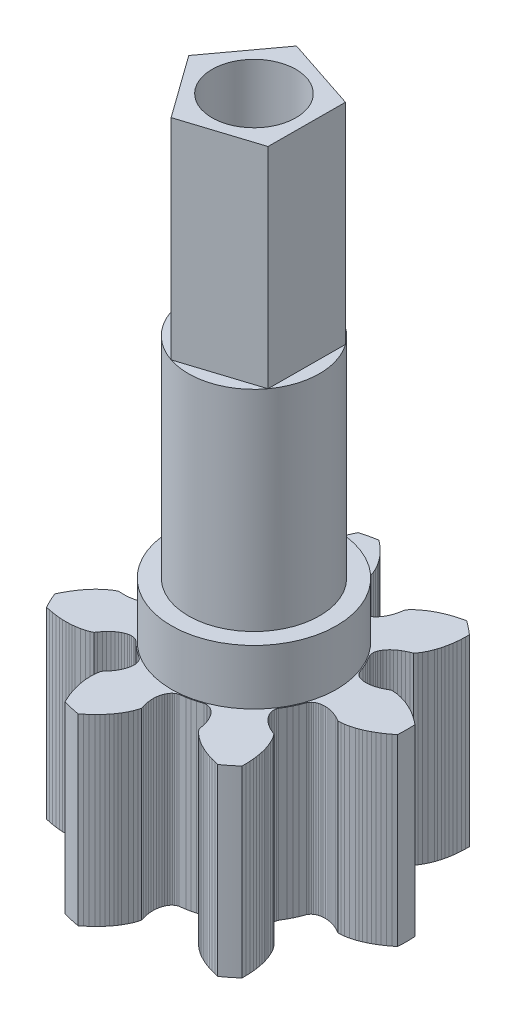
SolidWorks part; units mm, degrees
ref_plane "Front Plane" through (0, 0, 0) normal (0, 0, 1) x (1, 0, 0)
ref_plane "Top Plane" through (0, 0, 0) normal (0, 1, 0) x (1, 0, 0)
ref_plane "Right Plane" through (0, 0, 0) normal (1, 0, 0) x (0, 0, -1)
sketch "Sketch1" plane through (0, 0, 0) normal (0, 1, 0) x (1, 0, 0)
  circle A0 centre (0, 0) radius 3.15
  dimension "D1" = 6.3
extrude "Boss-Extrude1" add sketch "Sketch1" along normal blind 2.1
sketch "Sketch2" plane through (0, 2.1, 0) normal (0, 1, 0) x (1, 0, 0)
  circle A0 centre (0, 0) radius 2.5
  dimension "D1" = 5
extrude "Boss-Extrude3" add sketch "Sketch2" along normal blind 16
sketch "Sketch4" plane through (0, 0, 0) normal (0, -1, 0) x (1, 0, 0)
  line L420 (-1.6777, -5.4575) -> (-1.7402, -5.3144)
  line L421 (-1.7402, -5.3144) -> (-1.7939, -5.1757)
  line L422 (-1.7939, -5.1757) -> (-1.8392, -5.0423)
  line L423 (-1.8392, -5.0423) -> (-1.8764, -4.916)
  line L424 (-1.8764, -4.916) -> (-1.9071, -4.7932)
  line L425 (-1.9071, -4.7932) -> (-1.9311, -4.676)
  line L426 (-1.9311, -4.676) -> (-1.9488, -4.5668)
  line L427 (-1.9488, -4.5668) -> (-1.961, -4.464)
  line L428 (-1.961, -4.464) -> (-1.9715, -4.2798)
  line L429 (-1.9715, -4.2798) -> (-1.9674, -4.1246)
  line L430 (-1.9674, -4.1246) -> (-1.9537, -4.0009)
  line L431 (-1.9537, -4.0009) -> (-1.9303, -3.8867)
  line L432 (-1.9303, -3.8867) -> (-1.8594, -3.8097)
  line L433 (-1.8594, -3.8097) -> (-1.7784, -3.7125)
  line L434 (-1.7784, -3.7125) -> (-1.7087, -3.6155)
  line L435 (-1.7087, -3.6155) -> (-1.6501, -3.5195)
  line L436 (-1.6501, -3.5195) -> (-1.6023, -3.4251)
  line L437 (-1.6023, -3.4251) -> (-1.5652, -3.3333)
  line L438 (-1.5652, -3.3333) -> (-1.5384, -3.2446)
  line L439 (-1.5384, -3.2446) -> (-1.5215, -3.1597)
  line L440 (-1.5215, -3.1597) -> (-1.5143, -3.0795)
  line L441 (-1.5143, -3.0795) -> (-1.5162, -3.0043)
  line L442 (-1.5162, -3.0043) -> (-1.5269, -2.935)
  line L443 (-1.5269, -2.935) -> (-1.5457, -2.8721)
  line L444 (-1.5457, -2.8721) -> (-1.5723, -2.8162)
  line L445 (-1.5723, -2.8162) -> (-1.606, -2.7677)
  line L446 (-1.606, -2.7677) -> (-1.6572, -2.7183)
  line L447 (-1.6572, -2.7183) -> (-1.8447, -2.5928)
  line L448 (-1.8447, -2.5928) -> (-1.984, -2.4878)
  line L449 (-1.984, -2.4878) -> (-2.1173, -2.3754)
  line L450 (-2.1173, -2.3754) -> (-2.2814, -2.2205)
  line L451 (-2.2814, -2.2205) -> (-2.341, -2.1815)
  line L452 (-2.341, -2.1815) -> (-2.3957, -2.1595)
  line L453 (-2.3957, -2.1595) -> (-2.4562, -2.146)
  line L454 (-2.4562, -2.146) -> (-2.5217, -2.1417)
  line L455 (-2.5217, -2.1417) -> (-2.5917, -2.1467)
  line L456 (-2.5917, -2.1467) -> (-2.6653, -2.1615)
  line L457 (-2.6653, -2.1615) -> (-2.742, -2.1865)
  line L458 (-2.742, -2.1865) -> (-2.8209, -2.2218)
  line L459 (-2.8209, -2.2218) -> (-2.9014, -2.2676)
  line L460 (-2.9014, -2.2676) -> (-2.9827, -2.3243)
  line L461 (-2.9827, -2.3243) -> (-3.0641, -2.3918)
  line L462 (-3.0641, -2.3918) -> (-3.1447, -2.4703)
  line L463 (-3.1447, -2.4703) -> (-3.2237, -2.5599)
  line L464 (-3.2237, -2.5599) -> (-3.3005, -2.6605)
  line L465 (-3.3005, -2.6605) -> (-3.3598, -2.7467)
  line L466 (-3.3598, -2.7467) -> (-3.4659, -2.795)
  line L467 (-3.4659, -2.795) -> (-3.5835, -2.8358)
  line L468 (-3.5835, -2.8358) -> (-3.7338, -2.8744)
  line L469 (-3.7338, -2.8744) -> (-3.9158, -2.9052)
  line L470 (-3.9158, -2.9052) -> (-4.0187, -2.9161)
  line L471 (-4.0187, -2.9161) -> (-4.1291, -2.9232)
  line L472 (-4.1291, -2.9232) -> (-4.2487, -2.9258)
  line L473 (-4.2487, -2.9258) -> (-4.3752, -2.9233)
  line L474 (-4.3752, -2.9233) -> (-4.5067, -2.9151)
  line L475 (-4.5067, -2.9151) -> (-4.6468, -2.9006)
  line L476 (-4.6468, -2.9006) -> (-4.794, -2.8791)
  line L477 (-4.794, -2.8791) -> (-4.9474, -2.85)
  line L478 (-4.9474, -2.85) -> (-5.0902, -2.8167)
  line L479 (-5.3759, -2.2235) -> (-5.3129, -2.0911)
  line L480 (-5.3129, -2.0911) -> (-5.2399, -1.953)
  line L481 (-5.2399, -1.953) -> (-5.165, -1.8245)
  line L482 (-5.165, -1.8245) -> (-5.089, -1.7059)
  line L483 (-5.089, -1.7059) -> (-5.0134, -1.5981)
  line L484 (-5.0134, -1.5981) -> (-4.9365, -1.4976)
  line L485 (-4.9365, -1.4976) -> (-4.8599, -1.4057)
  line L486 (-4.8599, -1.4057) -> (-4.7855, -1.3238)
  line L487 (-4.7855, -1.3238) -> (-4.7128, -1.2502)
  line L488 (-4.7128, -1.2502) -> (-4.5753, -1.1271)
  line L489 (-4.5753, -1.1271) -> (-4.4514, -1.0336)
  line L490 (-4.4514, -1.0336) -> (-4.3462, -0.9671)
  line L491 (-4.3462, -0.9671) -> (-4.2422, -0.9142)
  line L492 (-4.2422, -0.9142) -> (-4.1379, -0.9217)
  line L493 (-4.1379, -0.9217) -> (-4.0114, -0.9244)
  line L494 (-4.0114, -0.9244) -> (-3.8921, -0.9184)
  line L495 (-3.8921, -0.9184) -> (-3.7804, -0.9043)
  line L496 (-3.7804, -0.9043) -> (-3.6769, -0.8828)
  line L497 (-3.6769, -0.8828) -> (-3.5819, -0.8546)
  line L498 (-3.5819, -0.8546) -> (-3.4959, -0.8203)
  line L499 (-3.4959, -0.8203) -> (-3.4191, -0.7805)
  line L500 (-3.4191, -0.7805) -> (-3.3518, -0.7361)
  line L501 (-3.3518, -0.7361) -> (-3.2942, -0.6878)
  line L502 (-3.2942, -0.6878) -> (-3.2467, -0.6363)
  line L503 (-3.2467, -0.6363) -> (-3.2093, -0.5823)
  line L504 (-3.2093, -0.5823) -> (-3.1821, -0.5267)
  line L505 (-3.1821, -0.5267) -> (-3.1652, -0.4701)
  line L506 (-3.1652, -0.4701) -> (-3.1585, -0.3992)
  line L507 (-3.1585, -0.3992) -> (-3.1773, -0.1744)
  line L508 (-3.1773, -0.1744) -> (-3.1821, 0)
  line L509 (-3.1821, 0) -> (-3.1773, 0.1743)
  line L510 (-3.1773, 0.1743) -> (-3.1585, 0.3991)
  line L511 (-3.1585, 0.3991) -> (-3.1652, 0.47)
  line L512 (-3.1652, 0.47) -> (-3.1821, 0.5266)
  line L513 (-3.1821, 0.5266) -> (-3.2093, 0.5822)
  line L514 (-3.2093, 0.5822) -> (-3.2467, 0.6362)
  line L515 (-3.2467, 0.6362) -> (-3.2942, 0.6877)
  line L516 (-3.2942, 0.6877) -> (-3.3518, 0.7361)
  line L517 (-3.3518, 0.7361) -> (-3.4191, 0.7805)
  line L518 (-3.4191, 0.7805) -> (-3.4959, 0.8202)
  line L519 (-3.4959, 0.8202) -> (-3.5819, 0.8545)
  line L520 (-3.5819, 0.8545) -> (-3.6769, 0.8828)
  line L521 (-3.6769, 0.8828) -> (-3.7804, 0.9043)
  line L522 (-3.7804, 0.9043) -> (-3.8921, 0.9183)
  line L523 (-3.8921, 0.9183) -> (-4.0114, 0.9243)
  line L524 (-4.0114, 0.9243) -> (-4.1379, 0.9216)
  line L525 (-4.1379, 0.9216) -> (-4.2422, 0.9142)
  line L526 (-4.2422, 0.9142) -> (-4.3462, 0.967)
  line L527 (-4.3462, 0.967) -> (-4.4514, 1.0335)
  line L528 (-4.4514, 1.0335) -> (-4.5753, 1.127)
  line L529 (-4.5753, 1.127) -> (-4.7128, 1.2501)
  line L530 (-4.7128, 1.2501) -> (-4.7855, 1.3238)
  line L531 (-4.7855, 1.3238) -> (-4.8599, 1.4056)
  line L532 (-4.8599, 1.4056) -> (-4.9365, 1.4975)
  line L533 (-4.9365, 1.4975) -> (-5.0134, 1.598)
  line L534 (-5.0134, 1.598) -> (-5.089, 1.7059)
  line L535 (-5.089, 1.7059) -> (-5.165, 1.8244)
  line L536 (-5.165, 1.8244) -> (-5.2399, 1.9529)
  line L537 (-5.2399, 1.9529) -> (-5.3129, 2.0911)
  line L538 (-5.3129, 2.0911) -> (-5.3759, 2.2234)
  line L539 (-5.0902, 2.8167) -> (-4.9474, 2.8499)
  line L540 (-4.9474, 2.8499) -> (-4.794, 2.879)
  line L541 (-4.794, 2.879) -> (-4.6468, 2.9005)
  line L542 (-4.6468, 2.9005) -> (-4.5067, 2.9151)
  line L543 (-4.5067, 2.9151) -> (-4.3752, 2.9232)
  line L544 (-4.3752, 2.9232) -> (-4.2487, 2.9257)
  line L545 (-4.2487, 2.9257) -> (-4.1291, 2.9231)
  line L546 (-4.1291, 2.9231) -> (-4.0187, 2.916)
  line L547 (-4.0187, 2.916) -> (-3.9158, 2.9051)
  line L548 (-3.9158, 2.9051) -> (-3.7338, 2.8743)
  line L549 (-3.7338, 2.8743) -> (-3.5835, 2.8358)
  line L550 (-3.5835, 2.8358) -> (-3.4659, 2.7949)
  line L551 (-3.4659, 2.7949) -> (-3.3598, 2.7466)
  line L552 (-3.3598, 2.7466) -> (-3.3005, 2.6604)
  line L553 (-3.3005, 2.6604) -> (-3.2237, 2.5598)
  line L554 (-3.2237, 2.5598) -> (-3.1447, 2.4703)
  line L555 (-3.1447, 2.4703) -> (-3.0641, 2.3918)
  line L556 (-3.0641, 2.3918) -> (-2.9827, 2.3242)
  line L557 (-2.9827, 2.3242) -> (-2.9014, 2.2676)
  line L558 (-2.9014, 2.2676) -> (-2.8209, 2.2217)
  line L559 (-2.8209, 2.2217) -> (-2.742, 2.1864)
  line L560 (-2.742, 2.1864) -> (-2.6653, 2.1615)
  line L561 (-2.6653, 2.1615) -> (-2.5917, 2.1466)
  line L562 (-2.5917, 2.1466) -> (-2.5217, 2.1416)
  line L563 (-2.5217, 2.1416) -> (-2.4562, 2.146)
  line L564 (-2.4562, 2.146) -> (-2.3957, 2.1594)
  line L565 (-2.3957, 2.1594) -> (-2.341, 2.1815)
  line L566 (-2.341, 2.1815) -> (-2.2814, 2.2205)
  line L567 (-2.2814, 2.2205) -> (-2.1173, 2.3753)
  line L568 (-2.1173, 2.3753) -> (-1.984, 2.4878)
  line L569 (-1.984, 2.4878) -> (-1.8447, 2.5927)
  line L570 (-1.8447, 2.5927) -> (-1.6572, 2.7182)
  line L571 (-1.6572, 2.7182) -> (-1.606, 2.7676)
  line L572 (-1.606, 2.7676) -> (-1.5723, 2.8161)
  line L573 (-1.5723, 2.8161) -> (-1.5457, 2.8721)
  line L574 (-1.5457, 2.8721) -> (-1.5269, 2.935)
  line L575 (-1.5269, 2.935) -> (-1.5162, 3.0043)
  line L576 (-1.5162, 3.0043) -> (-1.5143, 3.0794)
  line L577 (-1.5143, 3.0794) -> (-1.5215, 3.1597)
  line L578 (-1.5215, 3.1597) -> (-1.5384, 3.2445)
  line L579 (-1.5384, 3.2445) -> (-1.5652, 3.3332)
  line L580 (-1.5652, 3.3332) -> (-1.6023, 3.4251)
  line L581 (-1.6023, 3.4251) -> (-1.6501, 3.5194)
  line L582 (-1.6501, 3.5194) -> (-1.7087, 3.6154)
  line L583 (-1.7087, 3.6154) -> (-1.7784, 3.7125)
  line L584 (-1.7784, 3.7125) -> (-1.8594, 3.8097)
  line L585 (-1.8594, 3.8097) -> (-1.9303, 3.8866)
  line L586 (-1.9303, 3.8866) -> (-1.9537, 4.0009)
  line L587 (-1.9537, 4.0009) -> (-1.9674, 4.1246)
  line L588 (-1.9674, 4.1246) -> (-1.9715, 4.2797)
  line L589 (-1.9715, 4.2797) -> (-1.961, 4.464)
  line L590 (-1.961, 4.464) -> (-1.9488, 4.5668)
  line L591 (-1.9488, 4.5668) -> (-1.9311, 4.6759)
  line L592 (-1.9311, 4.6759) -> (-1.9071, 4.7932)
  line L593 (-1.9071, 4.7932) -> (-1.8764, 4.9159)
  line L594 (-1.8764, 4.9159) -> (-1.8392, 5.0423)
  line L595 (-1.8392, 5.0423) -> (-1.7939, 5.1756)
  line L596 (-1.7939, 5.1756) -> (-1.7402, 5.3143)
  line L597 (-1.7402, 5.3143) -> (-1.6777, 5.4575)
  line L598 (-1.6777, 5.4575) -> (-1.6135, 5.5893)
  line L599 (-0.9715, 5.7358) -> (-0.8565, 5.6449)
  line L600 (-0.8565, 5.6449) -> (-0.7381, 5.543)
  line L601 (-0.7381, 5.543) -> (-0.6295, 5.4414)
  line L602 (-0.6295, 5.4414) -> (-0.5308, 5.3409)
  line L603 (-0.5308, 5.3409) -> (-0.4425, 5.2432)
  line L604 (-0.4425, 5.2432) -> (-0.3616, 5.1459)
  line L605 (-0.3616, 5.1459) -> (-0.2891, 5.0507)
  line L606 (-0.2891, 5.0507) -> (-0.2258, 4.96)
  line L607 (-0.2258, 4.96) -> (-0.1702, 4.8727)
  line L608 (-0.1702, 4.8727) -> (-0.0808, 4.7113)
  line L609 (-0.0808, 4.7113) -> (-0.0172, 4.5697)
  line L610 (-0.0172, 4.5697) -> (0.0242, 4.4523)
  line L611 (0.0242, 4.4523) -> (0.0526, 4.3392)
  line L612 (0.0526, 4.3392) -> (0.0222, 4.2391)
  line L613 (0.0222, 4.2391) -> (-0.0086, 4.1164)
  line L614 (-0.0086, 4.1164) -> (-0.0293, 3.9987)
  line L615 (-0.0293, 3.9987) -> (-0.0405, 3.8868)
  line L616 (-0.0405, 3.8868) -> (-0.0426, 3.7811)
  line L617 (-0.0426, 3.7811) -> (-0.0362, 3.6822)
  line L618 (-0.0362, 3.6822) -> (-0.0218, 3.5907)
  line L619 (-0.0218, 3.5907) -> (-0.0002, 3.5069)
  line L620 (-0.0002, 3.5069) -> (0.0281, 3.4314)
  line L621 (0.0281, 3.4314) -> (0.0624, 3.3646)
  line L622 (0.0624, 3.3646) -> (0.1021, 3.3068)
  line L623 (0.1021, 3.3068) -> (0.1464, 3.2583)
  line L624 (0.1464, 3.2583) -> (0.1946, 3.2194)
  line L625 (0.1946, 3.2194) -> (0.246, 3.1903)
  line L626 (0.246, 3.1903) -> (0.3136, 3.1681)
  line L627 (0.3136, 3.1681) -> (0.537, 3.1363)
  line L628 (0.537, 3.1363) -> (0.708, 3.1022)
  line L629 (0.708, 3.1022) -> (0.8769, 3.0588)
  line L630 (0.8769, 3.0588) -> (1.0919, 2.9904)
  line L631 (1.0919, 2.9904) -> (1.1625, 2.9811)
  line L632 (1.1625, 2.9811) -> (1.2214, 2.985)
  line L633 (1.2214, 2.985) -> (1.2817, 2.9991)
  line L634 (1.2817, 2.9991) -> (1.3427, 3.0236)
  line L635 (1.3427, 3.0236) -> (1.4035, 3.0585)
  line L636 (1.4035, 3.0585) -> (1.4634, 3.1038)
  line L637 (1.4634, 3.1038) -> (1.5217, 3.1596)
  line L638 (1.5217, 3.1596) -> (1.5775, 3.2256)
  line L639 (1.5775, 3.2256) -> (1.6301, 3.3019)
  line L640 (1.6301, 3.3019) -> (1.6788, 3.3882)
  line L641 (1.6788, 3.3882) -> (1.7228, 3.4843)
  line L642 (1.7228, 3.4843) -> (1.7613, 3.59)
  line L643 (1.7613, 3.59) -> (1.7937, 3.705)
  line L644 (1.7937, 3.705) -> (1.8192, 3.829)
  line L645 (1.8192, 3.829) -> (1.8352, 3.9324)
  line L646 (1.8352, 3.9324) -> (1.9099, 4.0219)
  line L647 (1.9099, 4.0219) -> (1.9981, 4.1097)
  line L648 (1.9981, 4.1097) -> (2.1168, 4.2097)
  line L649 (2.1168, 4.2097) -> (2.2674, 4.3164)
  line L650 (2.2674, 4.3164) -> (2.3554, 4.3709)
  line L651 (2.3554, 4.3709) -> (2.4518, 4.4251)
  line L652 (2.4518, 4.4251) -> (2.5584, 4.4794)
  line L653 (2.5584, 4.4794) -> (2.6735, 4.532)
  line L654 (2.6735, 4.532) -> (2.7955, 4.5817)
  line L655 (2.7955, 4.5817) -> (2.928, 4.6294)
  line L656 (2.928, 4.6294) -> (3.0699, 4.6739)
  line L657 (3.0699, 4.6739) -> (3.2208, 4.7143)
  line L658 (3.2208, 4.7143) -> (3.3639, 4.7463)
  line L659 (3.8787, 4.3357) -> (3.8793, 4.1891)
  line L660 (3.8793, 4.1891) -> (3.8735, 4.033)
  line L661 (3.8735, 4.033) -> (3.8618, 3.8847)
  line L662 (3.8618, 3.8847) -> (3.8448, 3.7449)
  line L663 (3.8448, 3.7449) -> (3.8234, 3.615)
  line L664 (3.8234, 3.615) -> (3.7978, 3.4911)
  line L665 (3.7978, 3.4911) -> (3.7686, 3.375)
  line L666 (3.7686, 3.375) -> (3.7371, 3.269)
  line L667 (3.7371, 3.269) -> (3.7036, 3.1711)
  line L668 (3.7036, 3.1711) -> (3.6331, 3.0005)
  line L669 (3.6331, 3.0005) -> (3.562, 2.8625)
  line L670 (3.562, 2.8625) -> (3.4961, 2.757)
  line L671 (3.4961, 2.757) -> (3.4253, 2.6643)
  line L672 (3.4253, 2.6643) -> (3.3281, 2.6257)
  line L673 (3.3281, 2.6257) -> (3.213, 2.5732)
  line L674 (3.213, 2.5732) -> (3.1081, 2.516)
  line L675 (3.1081, 2.516) -> (3.0136, 2.4549)
  line L676 (3.0136, 2.4549) -> (2.9296, 2.3907)
  line L677 (2.9296, 2.3907) -> (2.8563, 2.324)
  line L678 (2.8563, 2.324) -> (2.7937, 2.2557)
  line L679 (2.7937, 2.2557) -> (2.7417, 2.1866)
  line L680 (2.7417, 2.1866) -> (2.7003, 2.1174)
  line L681 (2.7003, 2.1174) -> (2.6695, 2.0489)
  line L682 (2.6695, 2.0489) -> (2.649, 1.9819)
  line L683 (2.649, 1.9819) -> (2.6387, 1.917)
  line L684 (2.6387, 1.917) -> (2.6383, 1.8551)
  line L685 (2.6383, 1.8551) -> (2.6476, 1.7967)
  line L686 (2.6476, 1.7967) -> (2.6724, 1.73)
  line L687 (2.6724, 1.73) -> (2.7869, 1.5356)
  line L688 (2.7869, 1.5356) -> (2.8668, 1.3806)
  line L689 (2.8668, 1.3806) -> (2.9382, 1.2215)
  line L690 (2.9382, 1.2215) -> (3.0188, 1.0107)
  line L691 (3.0188, 1.0107) -> (3.0555, 0.9498)
  line L692 (3.0555, 0.9498) -> (3.0953, 0.9061)
  line L693 (3.0953, 0.9061) -> (3.144, 0.8678)
  line L694 (3.144, 0.8678) -> (3.2011, 0.8354)
  line L695 (3.2011, 0.8354) -> (3.2663, 0.8096)
  line L696 (3.2663, 0.8096) -> (3.3391, 0.791)
  line L697 (3.3391, 0.791) -> (3.419, 0.7802)
  line L698 (3.419, 0.7802) -> (3.5054, 0.7777)
  line L699 (3.5054, 0.7777) -> (3.5979, 0.7842)
  line L700 (3.5979, 0.7842) -> (3.6957, 0.7999)
  line L701 (3.6957, 0.7999) -> (3.7983, 0.8255)
  line L702 (3.7983, 0.8255) -> (3.905, 0.8612)
  line L703 (3.905, 0.8612) -> (4.0151, 0.9076)
  line L704 (4.0151, 0.9076) -> (4.1279, 0.9649)
  line L705 (4.1279, 0.9649) -> (4.2187, 1.0169)
  line L706 (4.2187, 1.0169) -> (4.3353, 1.0144)
  line L707 (4.3353, 1.0144) -> (4.4589, 1.0001)
  line L708 (4.4589, 1.0001) -> (4.6111, 0.9696)
  line L709 (4.6111, 0.9696) -> (4.7884, 0.9184)
  line L710 (4.7884, 0.9184) -> (4.8859, 0.8836)
  line L711 (4.8859, 0.8836) -> (4.9884, 0.8421)
  line L712 (4.9884, 0.8421) -> (5.0973, 0.7926)
  line L713 (5.0973, 0.7926) -> (5.2102, 0.7354)
  line L714 (5.2102, 0.7354) -> (5.3251, 0.671)
  line L715 (5.3251, 0.671) -> (5.445, 0.5972)
  line L716 (5.445, 0.5972) -> (5.5683, 0.5139)
  line L717 (5.5683, 0.5139) -> (5.6939, 0.4211)
  line L718 (5.6939, 0.4211) -> (5.8081, 0.3292)
  line L719 (5.8081, -0.3293) -> (5.6939, -0.4212)
  line L720 (5.6939, -0.4212) -> (5.5683, -0.514)
  line L721 (5.5683, -0.514) -> (5.445, -0.5972)
  line L722 (5.445, -0.5972) -> (5.3251, -0.6711)
  line L723 (5.3251, -0.6711) -> (5.2102, -0.7354)
  line L724 (5.2102, -0.7354) -> (5.0973, -0.7926)
  line L725 (5.0973, -0.7926) -> (4.9884, -0.8421)
  line L726 (4.9884, -0.8421) -> (4.8859, -0.8837)
  line L727 (4.8859, -0.8837) -> (4.7884, -0.9185)
  line L728 (4.7884, -0.9185) -> (4.6111, -0.9697)
  line L729 (4.6111, -0.9697) -> (4.4589, -1.0002)
  line L730 (4.4589, -1.0002) -> (4.3353, -1.0144)
  line L731 (4.3353, -1.0144) -> (4.2187, -1.017)
  line L732 (4.2187, -1.017) -> (4.1279, -0.965)
  line L733 (4.1279, -0.965) -> (4.0151, -0.9077)
  line L734 (4.0151, -0.9077) -> (3.905, -0.8613)
  line L735 (3.905, -0.8613) -> (3.7983, -0.8255)
  line L736 (3.7983, -0.8255) -> (3.6957, -0.8)
  line L737 (3.6957, -0.8) -> (3.5979, -0.7842)
  line L738 (3.5979, -0.7842) -> (3.5054, -0.7778)
  line L739 (3.5054, -0.7778) -> (3.419, -0.7803)
  line L740 (3.419, -0.7803) -> (3.3391, -0.7911)
  line L741 (3.3391, -0.7911) -> (3.2663, -0.8097)
  line L742 (3.2663, -0.8097) -> (3.2011, -0.8354)
  line L743 (3.2011, -0.8354) -> (3.144, -0.8678)
  line L744 (3.144, -0.8678) -> (3.0953, -0.9062)
  line L745 (3.0953, -0.9062) -> (3.0555, -0.9498)
  line L746 (3.0555, -0.9498) -> (3.0188, -1.0108)
  line L747 (3.0188, -1.0108) -> (2.9382, -1.2215)
  line L748 (2.9382, -1.2215) -> (2.8668, -1.3806)
  line L749 (2.8668, -1.3806) -> (2.7869, -1.5356)
  line L750 (2.7869, -1.5356) -> (2.6724, -1.7301)
  line L751 (2.6724, -1.7301) -> (2.6476, -1.7968)
  line L752 (2.6476, -1.7968) -> (2.6383, -1.8551)
  line L753 (2.6383, -1.8551) -> (2.6387, -1.9171)
  line L754 (2.6387, -1.9171) -> (2.649, -1.9819)
  line L755 (2.649, -1.9819) -> (2.6695, -2.049)
  line L756 (2.6695, -2.049) -> (2.7003, -2.1175)
  line L757 (2.7003, -2.1175) -> (2.7417, -2.1867)
  line L758 (2.7417, -2.1867) -> (2.7937, -2.2558)
  line L759 (2.7937, -2.2558) -> (2.8563, -2.3241)
  line L760 (2.8563, -2.3241) -> (2.9296, -2.3907)
  line L761 (2.9296, -2.3907) -> (3.0136, -2.455)
  line L762 (3.0136, -2.455) -> (3.1081, -2.5161)
  line L763 (3.1081, -2.5161) -> (3.213, -2.5733)
  line L764 (3.213, -2.5733) -> (3.3281, -2.6257)
  line L765 (3.3281, -2.6257) -> (3.4253, -2.6643)
  line L766 (3.4253, -2.6643) -> (3.4961, -2.757)
  line L767 (3.4961, -2.757) -> (3.562, -2.8626)
  line L768 (3.562, -2.8626) -> (3.6331, -3.0006)
  line L769 (3.6331, -3.0006) -> (3.7036, -3.1711)
  line L770 (3.7036, -3.1711) -> (3.7371, -3.2691)
  line L771 (3.7371, -3.2691) -> (3.7686, -3.3751)
  line L772 (3.7686, -3.3751) -> (3.7978, -3.4911)
  line L773 (3.7978, -3.4911) -> (3.8234, -3.615)
  line L774 (3.8234, -3.615) -> (3.8448, -3.745)
  line L775 (3.8448, -3.745) -> (3.8618, -3.8848)
  line L776 (3.8618, -3.8848) -> (3.8735, -4.0331)
  line L777 (3.8735, -4.0331) -> (3.8793, -4.1892)
  line L778 (3.8793, -4.1892) -> (3.8787, -4.3358)
  line L779 (3.3639, -4.7463) -> (3.2208, -4.7143)
  line L780 (3.2208, -4.7143) -> (3.0699, -4.6739)
  line L781 (3.0699, -4.6739) -> (2.928, -4.6295)
  line L782 (2.928, -4.6295) -> (2.7955, -4.5818)
  line L783 (2.7955, -4.5818) -> (2.6735, -4.5321)
  line L784 (2.6735, -4.5321) -> (2.5584, -4.4795)
  line L785 (2.5584, -4.4795) -> (2.4518, -4.4252)
  line L786 (2.4518, -4.4252) -> (2.3554, -4.3709)
  line L787 (2.3554, -4.3709) -> (2.2674, -4.3164)
  line L788 (2.2674, -4.3164) -> (2.1168, -4.2097)
  line L789 (2.1168, -4.2097) -> (1.9981, -4.1098)
  line L790 (1.9981, -4.1098) -> (1.9099, -4.022)
  line L791 (1.9099, -4.022) -> (1.8352, -3.9324)
  line L792 (1.8352, -3.9324) -> (1.8192, -3.829)
  line L793 (1.8192, -3.829) -> (1.7937, -3.7051)
  line L794 (1.7937, -3.7051) -> (1.7613, -3.5901)
  line L795 (1.7613, -3.5901) -> (1.7228, -3.4844)
  line L796 (1.7228, -3.4844) -> (1.6788, -3.3883)
  line L797 (1.6788, -3.3883) -> (1.6301, -3.3019)
  line L798 (1.6301, -3.3019) -> (1.5775, -3.2257)
  line L799 (1.5775, -3.2257) -> (1.5217, -3.1596)
  line L800 (1.5217, -3.1596) -> (1.4634, -3.1039)
  line L801 (1.4634, -3.1039) -> (1.4035, -3.0586)
  line L802 (1.4035, -3.0586) -> (1.3427, -3.0237)
  line L803 (1.3427, -3.0237) -> (1.2817, -2.9992)
  line L804 (1.2817, -2.9992) -> (1.2214, -2.9851)
  line L805 (1.2214, -2.9851) -> (1.1625, -2.9812)
  line L806 (1.1625, -2.9812) -> (1.0919, -2.9905)
  line L807 (1.0919, -2.9905) -> (0.8769, -3.0588)
  line L808 (0.8769, -3.0588) -> (0.708, -3.1023)
  line L809 (0.708, -3.1023) -> (0.537, -3.1364)
  line L810 (0.537, -3.1364) -> (0.3136, -3.1681)
  line L811 (0.3136, -3.1681) -> (0.246, -3.1904)
  line L812 (0.246, -3.1904) -> (0.1946, -3.2194)
  line L813 (0.1946, -3.2194) -> (0.1464, -3.2583)
  line L814 (0.1464, -3.2583) -> (0.1021, -3.3068)
  line L815 (0.1021, -3.3068) -> (0.0624, -3.3647)
  line L816 (0.0624, -3.3647) -> (0.0281, -3.4315)
  line L817 (0.0281, -3.4315) -> (-0.0002, -3.507)
  line L818 (-0.0002, -3.507) -> (-0.0218, -3.5907)
  line L819 (-0.0218, -3.5907) -> (-0.0362, -3.6823)
  line L820 (-0.0362, -3.6823) -> (-0.0426, -3.7811)
  line L821 (-0.0426, -3.7811) -> (-0.0405, -3.8868)
  line L822 (-0.0405, -3.8868) -> (-0.0293, -3.9988)
  line L823 (-0.0293, -3.9988) -> (-0.0086, -4.1165)
  line L824 (-0.0086, -4.1165) -> (0.0222, -4.2392)
  line L825 (0.0222, -4.2392) -> (0.0526, -4.3393)
  line L826 (0.0526, -4.3393) -> (0.0242, -4.4524)
  line L827 (0.0242, -4.4524) -> (-0.0172, -4.5698)
  line L828 (-0.0172, -4.5698) -> (-0.0808, -4.7113)
  line L829 (-0.0808, -4.7113) -> (-0.1702, -4.8728)
  line L830 (-0.1702, -4.8728) -> (-0.2258, -4.9601)
  line L831 (-0.2258, -4.9601) -> (-0.2891, -5.0508)
  line L832 (-0.2891, -5.0508) -> (-0.3616, -5.146)
  line L833 (-0.3616, -5.146) -> (-0.4425, -5.2433)
  line L834 (-0.4425, -5.2433) -> (-0.5308, -5.341)
  line L835 (-0.5308, -5.341) -> (-0.6295, -5.4414)
  line L836 (-0.6295, -5.4414) -> (-0.7381, -5.5431)
  line L837 (-0.7381, -5.5431) -> (-0.8565, -5.645)
  line L838 (-0.8565, -5.645) -> (-0.9715, -5.7359)
  line L839 (-1.6135, -5.5894) -> (-1.6777, -5.4575)
  arc A7 (-5.3759, -2.2235) -> (-5.0902, -2.8167) centre (0, 0) ccw
  arc A8 (-5.0902, 2.8167) -> (-5.3759, 2.2234) centre (0, -0.0001) ccw
  arc A9 (-0.9715, 5.7358) -> (-1.6135, 5.5893) centre (0, -0.0001) ccw
  arc A10 (3.8787, 4.3357) -> (3.3639, 4.7463) centre (-0.0001, -0.0001) ccw
  arc A11 (5.8081, -0.3293) -> (5.8081, 0.3292) centre (-0.0001, 0) ccw
  arc A12 (3.3639, -4.7463) -> (3.8787, -4.3358) centre (-0.0001, 0) ccw
  arc A13 (-1.6135, -5.5894) -> (-0.9715, -5.7359) centre (0, 0) ccw
extrude "Boss-Extrude4" add sketch "Sketch4" along normal blind 7
sketch "Sketch3" plane through (0, 0, 0) normal (0, -1, 0) x (1, 0, 0)
  circle A0 centre (0, 0) radius 1.1
  circle A1 centre (0, 0) radius 0.75
  dimension "D1" = 2.2
  dimension "D2" = 1.5
extrude "Cut-Extrude2" cut sketch "Sketch3" along normal through all contours A0 A1 | A1 region at (-1.0689, 0, 0) region at (0, 0, 0)
ref_plane "Plane2" through (0, 5.9, 0) normal (0, 1, 0) x (1, 0, 0)
sketch "Sketch6" plane through (0, -7, 0) normal (0, -1, 0) x (1, 0, 0)
  circle A0 centre (0, 0) radius 1.7
  dimension "D1" = 3.4
extrude "Cut-Extrude3" cut sketch "Sketch6" against normal offset from surface (7.6 mm away) 1.5 up to face at (0, 2.1, 2.5)
sketch "Sketch7" plane through (0, 0.6, 0) normal (0, -1, 0) x (1, 0, 0)
  circle A0 centre (0, 0) radius 1.6
  dimension "D1" = 3.2
ref_plane "Plane4" through (0, 8.1, 0) normal (0, 1, 0) x (1, 0, 0)
extrude "Cut-Extrude4" cut sketch "Sketch7" against normal through all
sketch "Sketch8" plane through (0, 18.1, 0) normal (0, 1, 0) x (1, 0, 0)
  line L1 (2.0145, -1.4804) -> (2.0305, 1.4584)
  line L2 (2.0305, 1.4584) -> (-0.7596, 2.3818)
  line L3 (-0.7596, 2.3818) -> (-2.5, 0.0136)
  line L4 (-2.5, 0.0136) -> (-0.7855, -2.3734)
  line L5 (-0.7855, -2.3734) -> (2.0145, -1.4804)
  circle A0 centre (0, 0) radius 2.5 construction
  circle A1 centre (0, 0) radius 2.5 construction
  circle A2 centre (0, 0) radius 2.5
extrude "Cut-Extrude5" cut sketch "Sketch8" against normal blind 8 flip side to cut contours L3 L4 L5 L1 L2
